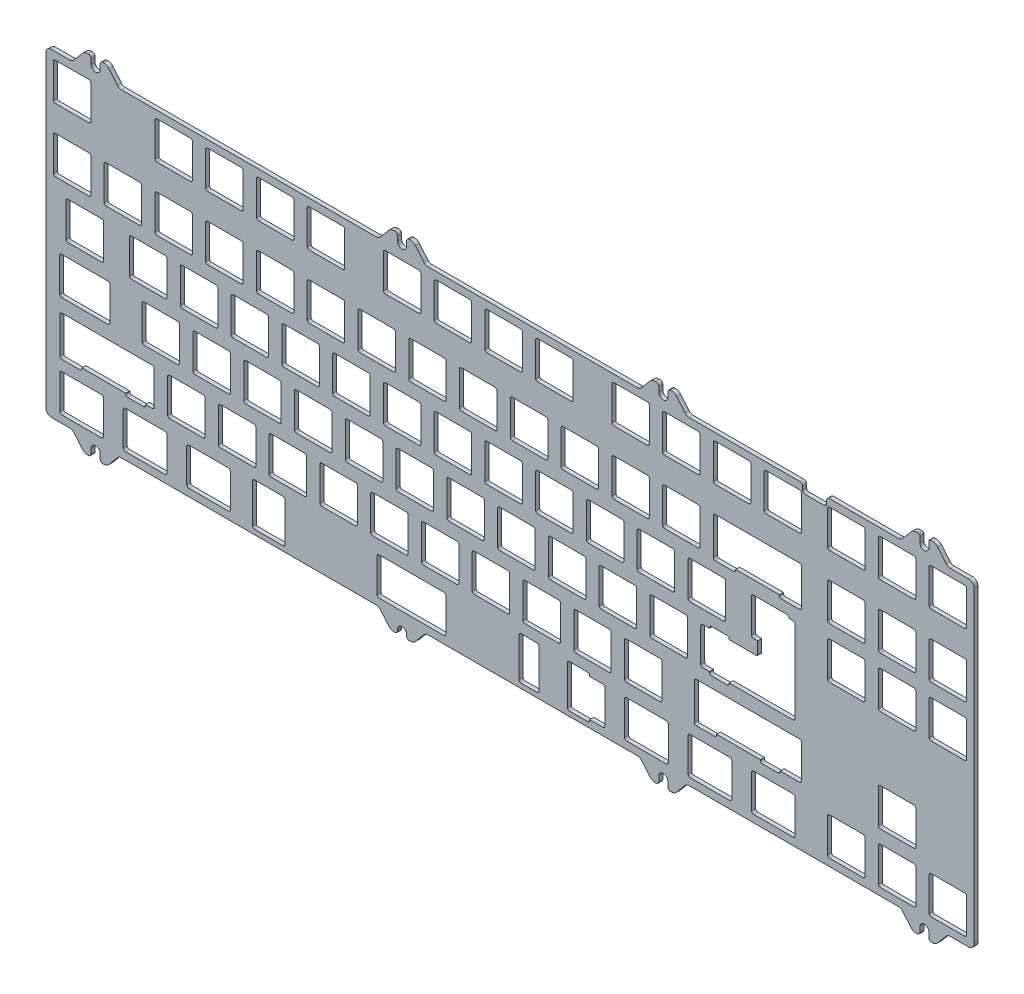
SolidWorks part; units mm, degrees
material "6061-T6 (SS)"
ref_plane "정면" through (0, 0, 0) normal (0, 0, 1) x (1, 0, 0)
ref_plane "윗면" through (0, 0, 0) normal (0, 1, 0) x (1, 0, 0)
ref_plane "우측면" through (0, 0, 0) normal (1, 0, 0) x (0, 0, -1)
sketch "스케치1" plane through (0, 0, 0) normal (0, 0, 1) x (1, 0, 0)
  line L450 (241.33, -16.7825) -> (273.02, -16.7825)
  line L451 (266.1131, -31.8325) -> (273.02, -31.8325)
  line L452 (231.5328, -109.8125) -> (310.0719, -109.8125)
  line L453 (234.2863, -73.9325) -> (272.92, -73.9325)
  line L454 (265.6692, -87.9825) -> (272.92, -87.9825)
  line L455 (255.7175, -92.9925) -> (270.5388, -92.9925)
  line L456 (255.7175, -107.0325) -> (270.5388, -107.0325)
  line L457 (260.37, -7.03) -> (273.03, -7.03)
  line L458 (260.37, 7.03) -> (273.03, 7.03)
  line L459 (231.5328, 9.8) -> (273.1063, 9.8)
  line L460 (246.5557, -68.9425) -> (270.5388, -68.9425)
  line L461 (255.6075, -35.8325) -> (268.2675, -35.8325)
  line L462 (18.5406, -109.8125) -> (114.1172, -109.8125)
  line L463 (27.0075, -68.9425) -> (39.6675, -68.9425)
  line L464 (27.0075, -54.8825) -> (39.6675, -54.8825)
  line L465 (31.77, -30.8425) -> (44.43, -30.8425)
  line L466 (31.77, -16.7825) -> (44.43, -16.7825)
  line L467 (31.77, -7.03) -> (44.43, -7.03)
  line L468 (31.77, 7.03) -> (44.43, 7.03)
  line L469 (18.5406, 9.8) -> (114.1172, 9.8)
  line L470 (-9.8, -107.8125) -> (-9.8, 7.8)
  line L471 (31.07, -17.4825) -> (31.07, -30.1425)
  line L472 (12.02, -17.4825) -> (12.02, -30.1425)
  line L473 (26.08, -17.4825) -> (26.08, -30.1425)
  line L474 (-7.03, -17.4825) -> (-7.03, -30.1425)
  line L475 (7.03, -17.4825) -> (7.03, -30.1425)
  line L476 (30.8125, -87.1825) -> (30.8125, -74.6325)
  line L477 (-4.6188, -88.2925) -> (-4.6188, -74.6325)
  line L478 (35.8325, -74.6325) -> (35.8325, -87.2925)
  line L479 (3.6682, -87.9925) -> (20.1443, -87.9925)
  line L480 (-3.8387, -92.9925) -> (10.9825, -92.9925)
  line L481 (-3.8387, -107.0325) -> (10.9825, -107.0325)
  line L482 (5.7546, -115.2125) -> (6.1328, -115.2125)
  line L483 (0.6572, -110.5269) -> (3.8395, -114.3195)
  line L484 (-0.8749, -109.8125) -> (-7.8, -109.8125)
  line L485 (2.9684, -88.9925) -> (-3.9188, -88.9925)
  line L486 (3.6682, -87.9925) -> (3.6684, -88.2921)
  line L487 (-4.6387, -93.7925) -> (-4.6387, -106.2325)
  line L488 (10.5328, -112.4125) -> (10.5328, -114.2125)
  line L489 (7.1328, -112.4125) -> (7.1328, -114.2125)
  line L490 (17.0085, -110.5269) -> (13.8262, -114.3195)
  line L491 (11.5328, -115.2125) -> (11.9111, -115.2125)
  line L492 (20.8441, -88.9925) -> (26.8442, -88.9925)
  line L493 (19.9738, -92.9925) -> (34.795, -92.9925)
  line L494 (19.9738, -107.0325) -> (34.795, -107.0325)
  line L495 (20.1443, -87.9925) -> (20.1441, -88.2921)
  line L496 (19.1738, -93.7925) -> (19.1738, -106.2325)
  line L497 (11.7825, -93.7925) -> (11.7825, -106.2325)
  line L498 (27.5442, -88.2925) -> (27.5442, -87.9825)
  line L499 (27.5442, -87.9825) -> (30.0125, -87.9825)
  line L500 (35.595, -93.7925) -> (35.595, -106.2325)
  line L501 (30.1125, -73.9325) -> (-3.9188, -73.9325)
  line L502 (-3.9488, -68.9425) -> (13.4737, -68.9425)
  line L503 (-3.9488, -54.8825) -> (13.4737, -54.8825)
  line L504 (-1.5675, -49.8925) -> (11.0925, -49.8925)
  line L505 (-1.5675, -35.8325) -> (11.0925, -35.8325)
  line L506 (-4.6488, -55.5825) -> (-4.6488, -68.2425)
  line L507 (-6.33, -30.8425) -> (6.33, -30.8425)
  line L508 (-2.2675, -36.5325) -> (-2.2675, -49.1925)
  line L509 (26.3075, -55.5825) -> (26.3075, -68.2425)
  line L510 (14.1737, -55.5825) -> (14.1737, -68.2425)
  line L511 (12.72, -30.8425) -> (25.38, -30.8425)
  line L512 (21.545, -36.5325) -> (21.545, -49.1925)
  line L513 (11.7925, -36.5325) -> (11.7925, -49.1925)
  line L514 (35.605, -36.5325) -> (35.605, -49.1925)
  line L515 (22.245, -49.8925) -> (34.905, -49.8925)
  line L516 (22.245, -35.8325) -> (34.905, -35.8325)
  line L517 (-7.03, 6.33) -> (-7.03, -6.33)
  line L518 (7.03, 6.33) -> (7.03, -6.33)
  line L519 (-6.33, -16.7825) -> (6.33, -16.7825)
  line L520 (-6.33, -7.03) -> (6.33, -7.03)
  line L521 (-0.8749, 9.8) -> (-7.8, 9.8)
  line L522 (-6.33, 7.03) -> (6.33, 7.03)
  line L523 (5.7546, 15.2) -> (6.1328, 15.2)
  line L524 (0.6572, 10.5144) -> (3.8395, 14.307)
  line L525 (31.07, 6.33) -> (31.07, -6.33)
  line L526 (12.72, -16.7825) -> (25.38, -16.7825)
  line L527 (11.5328, 15.2) -> (11.9111, 15.2)
  line L528 (10.5328, 12.4) -> (10.5328, 14.2)
  line L529 (7.1328, 12.4) -> (7.1328, 14.2)
  line L530 (17.0085, 10.5144) -> (13.8262, 14.307)
  line L531 (240.63, -17.4825) -> (240.63, -31.1325)
  line L532 (221.57, -17.4825) -> (221.57, -30.1425)
  line L533 (235.63, -17.4825) -> (235.63, -30.1425)
  line L534 (202.52, -17.4825) -> (202.52, -30.1425)
  line L535 (216.58, -17.4825) -> (216.58, -30.1425)
  line L536 (183.47, -17.4825) -> (183.47, -30.1425)
  line L537 (197.53, -17.4825) -> (197.53, -30.1425)
  line L538 (164.42, -17.4825) -> (164.42, -30.1425)
  line L539 (178.48, -17.4825) -> (178.48, -30.1425)
  line L540 (145.37, -17.4825) -> (145.37, -30.1425)
  line L541 (159.43, -17.4825) -> (159.43, -30.1425)
  line L542 (126.32, -17.4825) -> (126.32, -30.1425)
  line L543 (140.38, -17.4825) -> (140.38, -30.1425)
  line L544 (107.27, -17.4825) -> (107.27, -30.1425)
  line L545 (121.33, -17.4825) -> (121.33, -30.1425)
  line L546 (88.22, -17.4825) -> (88.22, -30.1425)
  line L547 (102.28, -17.4825) -> (102.28, -30.1425)
  line L548 (69.17, -17.4825) -> (69.17, -30.1425)
  line L549 (83.23, -17.4825) -> (83.23, -30.1425)
  line L550 (50.12, -17.4825) -> (50.12, -30.1425)
  line L551 (64.18, -17.4825) -> (64.18, -30.1425)
  line L552 (45.13, -17.4825) -> (45.13, -30.1425)
  line L553 (133.5328, -109.8125) -> (212.1172, -109.8125)
  line L554 (150.8325, -87.9925) -> (163.4925, -87.9925)
  line L555 (150.8325, -73.9325) -> (163.4925, -73.9325)
  line L556 (141.3075, -68.9425) -> (153.9675, -68.9425)
  line L557 (141.3075, -54.8825) -> (153.9675, -54.8825)
  line L558 (146.07, -30.8425) -> (158.73, -30.8425)
  line L559 (93.6825, -87.9925) -> (106.3425, -87.9925)
  line L560 (93.6825, -73.9325) -> (106.3425, -73.9325)
  line L561 (84.1575, -68.9425) -> (96.8175, -68.9425)
  line L562 (84.1575, -54.8825) -> (96.8175, -54.8825)
  line L563 (88.92, -30.8425) -> (101.58, -30.8425)
  line L564 (92.9825, -74.6325) -> (92.9825, -87.2925)
  line L565 (73.9325, -74.6325) -> (73.9325, -87.2925)
  line L566 (87.9925, -74.6325) -> (87.9925, -87.2925)
  line L567 (54.8825, -74.6325) -> (54.8825, -87.2925)
  line L568 (68.9425, -74.6325) -> (68.9425, -87.2925)
  line L569 (49.8925, -74.6325) -> (49.8925, -87.2925)
  line L570 (55.5825, -87.9925) -> (68.2425, -87.9925)
  line L571 (43.7863, -92.9925) -> (58.6075, -92.9925)
  line L572 (43.7863, -107.0325) -> (58.6075, -107.0325)
  line L573 (42.9863, -93.7925) -> (42.9863, -106.2325)
  line L574 (36.5325, -87.9925) -> (49.1925, -87.9925)
  line L575 (59.4075, -93.7925) -> (59.4075, -106.2325)
  line L576 (74.6325, -87.9925) -> (87.2925, -87.9925)
  line L577 (68.374, -91.9925) -> (79.1683, -91.9925)
  line L578 (68.374, -108.0325) -> (79.1683, -108.0325)
  line L579 (67.674, -107.3325) -> (67.674, -92.6925)
  line L580 (79.8683, -107.3325) -> (79.8683, -92.6925)
  line L581 (55.5825, -73.9325) -> (68.2425, -73.9325)
  line L582 (60.345, -49.8925) -> (73.005, -49.8925)
  line L583 (60.345, -35.8325) -> (73.005, -35.8325)
  line L584 (64.4075, -55.5825) -> (64.4075, -68.2425)
  line L585 (45.3575, -55.5825) -> (45.3575, -68.2425)
  line L586 (59.4175, -55.5825) -> (59.4175, -68.2425)
  line L587 (40.3675, -55.5825) -> (40.3675, -68.2425)
  line L588 (46.0575, -68.9425) -> (58.7175, -68.9425)
  line L589 (36.5325, -73.9325) -> (49.1925, -73.9325)
  line L590 (46.0575, -54.8825) -> (58.7175, -54.8825)
  line L591 (41.295, -49.8925) -> (53.955, -49.8925)
  line L592 (41.295, -35.8325) -> (53.955, -35.8325)
  line L593 (40.595, -36.5325) -> (40.595, -49.1925)
  line L594 (59.645, -36.5325) -> (59.645, -49.1925)
  line L595 (54.655, -36.5325) -> (54.655, -49.1925)
  line L596 (50.82, -30.8425) -> (63.48, -30.8425)
  line L597 (83.4575, -55.5825) -> (83.4575, -68.2425)
  line L598 (78.4675, -55.5825) -> (78.4675, -68.2425)
  line L599 (74.6325, -73.9325) -> (87.2925, -73.9325)
  line L600 (65.1075, -68.9425) -> (77.7675, -68.9425)
  line L601 (69.87, -30.8425) -> (82.53, -30.8425)
  line L602 (65.1075, -54.8825) -> (77.7675, -54.8825)
  line L603 (78.695, -36.5325) -> (78.695, -49.1925)
  line L604 (73.705, -36.5325) -> (73.705, -49.1925)
  line L605 (92.755, -36.5325) -> (92.755, -49.1925)
  line L606 (79.395, -49.8925) -> (92.055, -49.8925)
  line L607 (79.395, -35.8325) -> (92.055, -35.8325)
  line L608 (150.1325, -74.6325) -> (150.1325, -87.2925)
  line L609 (131.0825, -74.6325) -> (131.0825, -87.2925)
  line L610 (145.1425, -74.6325) -> (145.1425, -87.2925)
  line L611 (112.0325, -74.6325) -> (112.0325, -87.2925)
  line L612 (126.0925, -74.6325) -> (126.0925, -87.2925)
  line L613 (107.0425, -74.6325) -> (107.0425, -87.2925)
  line L614 (115.2238, -92.9925) -> (139.57, -92.9925)
  line L615 (115.2238, -107.0325) -> (139.57, -107.0325)
  line L616 (112.7325, -87.9925) -> (125.3925, -87.9925)
  line L617 (122.125, -113.7125) -> (122.125, -114.2125)
  line L618 (115.6493, -110.5269) -> (118.8316, -114.3195)
  line L619 (120.7468, -115.2125) -> (121.125, -115.2125)
  line L620 (114.4238, -93.7925) -> (114.4238, -106.2325)
  line L621 (125.525, -113.7125) -> (125.525, -114.2125)
  line L622 (132.0007, -110.5269) -> (128.8184, -114.3195)
  line L623 (126.525, -115.2125) -> (126.9033, -115.2125)
  line L624 (131.7825, -87.9925) -> (144.4425, -87.9925)
  line L625 (140.37, -93.7925) -> (140.37, -106.2325)
  line L626 (112.7325, -73.9325) -> (125.3925, -73.9325)
  line L627 (122.2575, -68.9425) -> (134.9175, -68.9425)
  line L628 (122.2575, -54.8825) -> (134.9175, -54.8825)
  line L629 (117.495, -49.8925) -> (130.155, -49.8925)
  line L630 (117.495, -35.8325) -> (130.155, -35.8325)
  line L631 (121.5575, -55.5825) -> (121.5575, -68.2425)
  line L632 (102.5075, -55.5825) -> (102.5075, -68.2425)
  line L633 (116.5675, -55.5825) -> (116.5675, -68.2425)
  line L634 (97.5175, -55.5825) -> (97.5175, -68.2425)
  line L635 (103.2075, -68.9425) -> (115.8675, -68.9425)
  line L636 (103.2075, -54.8825) -> (115.8675, -54.8825)
  line L637 (98.445, -49.8925) -> (111.105, -49.8925)
  line L638 (98.445, -35.8325) -> (111.105, -35.8325)
  line L639 (107.97, -30.8425) -> (120.63, -30.8425)
  line L640 (97.745, -36.5325) -> (97.745, -49.1925)
  line L641 (116.795, -36.5325) -> (116.795, -49.1925)
  line L642 (111.805, -36.5325) -> (111.805, -49.1925)
  line L643 (140.6075, -55.5825) -> (140.6075, -68.2425)
  line L644 (135.6175, -55.5825) -> (135.6175, -68.2425)
  line L645 (131.7825, -73.9325) -> (144.4425, -73.9325)
  line L646 (136.545, -49.8925) -> (149.205, -49.8925)
  line L647 (136.545, -35.8325) -> (149.205, -35.8325)
  line L648 (127.02, -30.8425) -> (139.68, -30.8425)
  line L649 (135.845, -36.5325) -> (135.845, -49.1925)
  line L650 (130.855, -36.5325) -> (130.855, -49.1925)
  line L651 (149.905, -36.5325) -> (149.905, -49.1925)
  line L652 (208.0925, -92.9925) -> (222.9138, -92.9925)
  line L653 (208.0925, -107.0325) -> (222.9138, -107.0325)
  line L654 (207.9825, -87.9925) -> (220.6425, -87.9925)
  line L655 (207.9825, -73.9325) -> (220.6425, -73.9325)
  line L656 (198.4575, -54.8825) -> (211.1175, -54.8825)
  line L657 (203.22, -30.8425) -> (215.88, -30.8425)
  line L658 (198.4575, -68.9425) -> (211.1175, -68.9425)
  line L659 (207.2825, -74.6325) -> (207.2825, -87.2925)
  line L660 (188.2325, -74.6325) -> (188.2325, -87.2925)
  line L661 (202.2925, -74.6325) -> (202.2925, -87.2925)
  line L662 (169.1825, -74.6325) -> (169.1825, -87.2925)
  line L663 (183.2425, -74.6325) -> (183.2425, -87.2925)
  line L664 (164.1925, -74.6325) -> (164.1925, -87.2925)
  line L665 (169.8825, -87.9925) -> (182.5425, -87.9925)
  line L666 (174.45, -108.0325) -> (168.45, -108.0325)
  line L667 (168.45, -91.9925) -> (174.45, -91.9925)
  line L668 (175.15, -107.3325) -> (175.15, -92.6925)
  line L669 (167.75, -107.3325) -> (167.75, -92.6925)
  line L670 (199.1013, -92.9925) -> (194.168, -92.9925)
  line L671 (188.9325, -87.9925) -> (201.5925, -87.9925)
  line L672 (194.168, -107.0325) -> (199.1013, -107.0325)
  line L673 (186.5613, -91.9925) -> (193.468, -91.9925)
  line L674 (194.168, -107.0325) -> (194.168, -107.3325)
  line L675 (186.5613, -108.0325) -> (193.468, -108.0325)
  line L676 (194.168, -92.9925) -> (194.168, -92.6925)
  line L677 (185.8613, -92.6925) -> (185.8613, -107.3325)
  line L678 (199.9013, -93.7925) -> (199.9013, -106.2325)
  line L679 (207.2925, -93.7925) -> (207.2925, -106.2325)
  line L680 (169.8825, -73.9325) -> (182.5425, -73.9325)
  line L681 (179.4075, -68.9425) -> (192.0675, -68.9425)
  line L682 (179.4075, -54.8825) -> (192.0675, -54.8825)
  line L683 (174.645, -49.8925) -> (187.305, -49.8925)
  line L684 (174.645, -35.8325) -> (187.305, -35.8325)
  line L685 (178.7075, -55.5825) -> (178.7075, -68.2425)
  line L686 (159.6575, -55.5825) -> (159.6575, -68.2425)
  line L687 (173.7175, -55.5825) -> (173.7175, -68.2425)
  line L688 (154.6675, -55.5825) -> (154.6675, -68.2425)
  line L689 (160.3575, -68.9425) -> (173.0175, -68.9425)
  line L690 (160.3575, -54.8825) -> (173.0175, -54.8825)
  line L691 (155.595, -49.8925) -> (168.255, -49.8925)
  line L692 (155.595, -35.8325) -> (168.255, -35.8325)
  line L693 (165.12, -30.8425) -> (177.78, -30.8425)
  line L694 (154.895, -36.5325) -> (154.895, -49.1925)
  line L695 (173.945, -36.5325) -> (173.945, -49.1925)
  line L696 (168.955, -36.5325) -> (168.955, -49.1925)
  line L697 (192.7675, -55.5825) -> (192.7675, -68.2425)
  line L698 (197.7575, -55.5825) -> (197.7575, -68.2425)
  line L699 (188.9325, -73.9325) -> (201.5925, -73.9325)
  line L700 (193.695, -49.8925) -> (206.355, -49.8925)
  line L701 (193.695, -35.8325) -> (206.355, -35.8325)
  line L702 (184.17, -30.8425) -> (196.83, -30.8425)
  line L703 (192.995, -36.5325) -> (192.995, -49.1925)
  line L704 (188.005, -36.5325) -> (188.005, -49.1925)
  line L705 (207.055, -36.5325) -> (207.055, -49.1925)
  line L706 (233.4863, -74.7325) -> (233.4863, -88.2925)
  line L707 (221.3425, -74.6325) -> (221.3425, -87.2925)
  line L708 (234.1863, -88.9925) -> (241.0932, -88.9925)
  line L709 (231.905, -92.9925) -> (246.7263, -92.9925)
  line L710 (231.905, -107.0325) -> (246.7263, -107.0325)
  line L711 (223.525, -112.4125) -> (223.525, -114.2125)
  line L712 (220.125, -112.4125) -> (220.125, -114.2125)
  line L713 (213.6493, -110.5269) -> (216.8316, -114.3195)
  line L714 (219.125, -115.2125) -> (218.7468, -115.2125)
  line L715 (230.0007, -110.5269) -> (226.8184, -114.3195)
  line L716 (224.9033, -115.2125) -> (224.525, -115.2125)
  line L717 (231.105, -93.7925) -> (231.105, -106.2325)
  line L718 (223.7138, -93.7925) -> (223.7138, -106.2325)
  line L719 (241.7932, -87.9925) -> (258.2693, -87.9925)
  line L720 (241.7932, -88.2925) -> (241.7932, -87.9925)
  line L721 (247.5263, -93.7925) -> (247.5263, -106.2325)
  line L722 (258.9693, -88.9925) -> (264.9692, -88.9925)
  line L723 (258.2693, -88.2925) -> (258.2693, -87.9925)
  line L724 (265.6692, -88.2925) -> (265.6692, -87.9825)
  line L725 (254.9175, -93.7925) -> (254.9175, -106.2325)
  line L726 (231.795, -49.8925) -> (244.455, -49.8925)
  line L727 (231.795, -35.8325) -> (244.455, -35.8325)
  line L728 (236.6675, -68.9425) -> (239.1558, -68.9425)
  line L729 (236.6675, -54.8825) -> (239.1558, -54.8825)
  line L730 (216.8075, -55.5825) -> (216.8075, -68.2425)
  line L731 (230.8675, -55.5825) -> (230.8675, -68.2425)
  line L732 (211.8175, -55.5825) -> (211.8175, -68.2425)
  line L733 (217.5075, -68.9425) -> (230.1675, -68.9425)
  line L734 (235.8675, -55.6825) -> (235.8675, -68.1425)
  line L735 (212.745, -49.8925) -> (225.405, -49.8925)
  line L736 (212.745, -35.8325) -> (225.405, -35.8325)
  line L737 (222.27, -30.8425) -> (234.93, -30.8425)
  line L738 (217.5075, -54.8825) -> (230.1675, -54.8825)
  line L739 (212.045, -36.5325) -> (212.045, -49.1925)
  line L740 (231.095, -36.5325) -> (231.095, -49.1925)
  line L741 (226.105, -36.5325) -> (226.105, -49.1925)
  line L742 (239.8558, -69.9425) -> (245.8557, -69.9425)
  line L743 (246.5557, -69.2425) -> (246.5557, -68.9425)
  line L744 (239.1558, -69.2425) -> (239.1558, -68.9425)
  line L745 (248.937, -30.8325) -> (265.4131, -30.8325)
  line L746 (246.5557, -54.8825) -> (256.767, -54.8825)
  line L747 (248.937, -31.1325) -> (248.937, -30.8325)
  line L748 (241.33, -31.8325) -> (248.237, -31.8325)
  line L749 (239.8558, -53.8825) -> (245.8557, -53.8825)
  line L750 (246.5557, -54.5825) -> (246.5557, -54.8825)
  line L751 (239.1558, -54.5825) -> (239.1558, -54.8825)
  line L752 (245.155, -36.5325) -> (245.155, -49.1925)
  line L753 (265.4131, -31.1325) -> (265.4131, -30.8325)
  line L754 (254.9075, -36.5325) -> (254.9075, -49.1925)
  line L755 (255.6075, -49.8925) -> (257.267, -49.8925)
  line L756 (257.267, -49.8925) -> (257.267, -54.3825)
  line L757 (146.07, -16.7825) -> (158.73, -16.7825)
  line L758 (133.5328, 9.8) -> (212.1172, 9.8)
  line L759 (88.92, -16.7825) -> (101.58, -16.7825)
  line L760 (88.92, -7.03) -> (101.58, -7.03)
  line L761 (88.92, 7.03) -> (101.58, 7.03)
  line L762 (50.12, 6.33) -> (50.12, -6.33)
  line L763 (64.18, 6.33) -> (64.18, -6.33)
  line L764 (45.13, 6.33) -> (45.13, -6.33)
  line L765 (50.82, -16.7825) -> (63.48, -16.7825)
  line L766 (50.82, -7.03) -> (63.48, -7.03)
  line L767 (50.82, 7.03) -> (63.48, 7.03)
  line L768 (88.22, 6.33) -> (88.22, -6.33)
  line L769 (69.17, 6.33) -> (69.17, -6.33)
  line L770 (83.23, 6.33) -> (83.23, -6.33)
  line L771 (69.87, -16.7825) -> (82.53, -16.7825)
  line L772 (69.87, -7.03) -> (82.53, -7.03)
  line L773 (69.87, 7.03) -> (82.53, 7.03)
  line L774 (117.495, -7.03) -> (130.155, -7.03)
  line L775 (117.495, 7.03) -> (130.155, 7.03)
  line L776 (116.795, 6.33) -> (116.795, -6.33)
  line L777 (102.28, 6.33) -> (102.28, -6.33)
  line L778 (107.97, -16.7825) -> (120.63, -16.7825)
  line L779 (122.125, 12.4) -> (122.125, 14.2)
  line L780 (120.7468, 15.2) -> (121.125, 15.2)
  line L781 (115.6493, 10.5144) -> (118.8316, 14.307)
  line L782 (135.845, 6.33) -> (135.845, -6.33)
  line L783 (149.905, 6.33) -> (149.905, -6.33)
  line L784 (130.855, 6.33) -> (130.855, -6.33)
  line L785 (127.02, -16.7825) -> (139.68, -16.7825)
  line L786 (136.545, -7.03) -> (149.205, -7.03)
  line L787 (136.545, 7.03) -> (149.205, 7.03)
  line L788 (125.525, 12.4) -> (125.525, 14.2)
  line L789 (126.525, 15.2) -> (126.9033, 15.2)
  line L790 (132.0007, 10.5144) -> (128.8184, 14.307)
  line L791 (203.22, -16.7825) -> (215.88, -16.7825)
  line L792 (203.22, -7.03) -> (215.88, -7.03)
  line L793 (203.22, 7.03) -> (215.88, 7.03)
  line L794 (174.645, -7.03) -> (187.305, -7.03)
  line L795 (174.645, 7.03) -> (187.305, 7.03)
  line L796 (173.945, 6.33) -> (173.945, -6.33)
  line L797 (154.895, 6.33) -> (154.895, -6.33)
  line L798 (168.955, 6.33) -> (168.955, -6.33)
  line L799 (165.12, -16.7825) -> (177.78, -16.7825)
  line L800 (155.595, -7.03) -> (168.255, -7.03)
  line L801 (155.595, 7.03) -> (168.255, 7.03)
  line L802 (202.52, 6.33) -> (202.52, -6.33)
  line L803 (188.005, 6.33) -> (188.005, -6.33)
  line L804 (184.17, -16.7825) -> (196.83, -16.7825)
  line L805 (221.57, 6.33) -> (221.57, -6.33)
  line L806 (235.63, 6.33) -> (235.63, -6.33)
  line L807 (216.58, 6.33) -> (216.58, -6.33)
  line L808 (222.27, -16.7825) -> (234.93, -16.7825)
  line L809 (222.27, -7.03) -> (234.93, -7.03)
  line L810 (222.27, 7.03) -> (234.93, 7.03)
  line L811 (223.525, 12.4) -> (223.525, 14.2)
  line L812 (219.125, 15.2) -> (218.7468, 15.2)
  line L813 (220.125, 12.4) -> (220.125, 14.2)
  line L814 (213.6493, 10.5144) -> (216.8316, 14.307)
  line L815 (224.9033, 15.2) -> (224.525, 15.2)
  line L816 (230.0007, 10.5144) -> (226.8184, 14.307)
  line L817 (259.67, 6.33) -> (259.67, -6.33)
  line L818 (240.62, 6.33) -> (240.62, -6.33)
  line L819 (254.68, 6.33) -> (254.68, -6.33)
  line L820 (241.32, -7.03) -> (253.98, -7.03)
  line L821 (241.32, 7.03) -> (253.98, 7.03)
  line L822 (273.72, -17.4825) -> (273.72, -31.1325)
  line L823 (338.4125, -107.8125) -> (338.4125, 7.8)
  line L824 (321.5825, -17.4825) -> (321.5825, -30.1425)
  line L825 (335.6425, -17.4825) -> (335.6425, -30.1425)
  line L826 (302.5325, -17.4825) -> (302.5325, -30.1425)
  line L827 (316.5925, -17.4825) -> (316.5925, -30.1425)
  line L828 (283.4825, -17.4825) -> (283.4825, -30.1425)
  line L829 (297.5425, -17.4825) -> (297.5425, -30.1425)
  line L830 (322.2825, -107.0425) -> (334.9425, -107.0425)
  line L831 (322.2825, -92.9825) -> (334.9425, -92.9825)
  line L832 (322.2825, -49.8925) -> (334.9425, -49.8925)
  line L833 (322.2825, -35.8325) -> (334.9425, -35.8325)
  line L834 (322.2825, -30.8425) -> (334.9425, -30.8425)
  line L835 (302.5325, -74.6325) -> (302.5325, -87.2925)
  line L836 (316.5925, -74.6325) -> (316.5925, -87.2925)
  line L837 (273.72, -74.7325) -> (273.72, -87.1825)
  line L838 (284.1825, -107.0425) -> (296.8425, -107.0425)
  line L839 (284.1825, -92.9825) -> (296.8425, -92.9825)
  line L840 (271.3388, -93.7925) -> (271.3388, -106.2325)
  line L841 (283.4825, -93.6825) -> (283.4825, -106.3425)
  line L842 (322.8579, -115.2125) -> (322.4797, -115.2125)
  line L843 (321.4797, -112.4125) -> (321.4797, -114.2125)
  line L844 (318.0797, -112.4125) -> (318.0797, -114.2125)
  line L845 (311.604, -110.5269) -> (314.7863, -114.3195)
  line L846 (317.0797, -115.2125) -> (316.7014, -115.2125)
  line L847 (303.2325, -107.0425) -> (315.8925, -107.0425)
  line L848 (303.2325, -92.9825) -> (315.8925, -92.9825)
  line L849 (303.2325, -87.9925) -> (315.8925, -87.9925)
  line L850 (302.5325, -93.6825) -> (302.5325, -106.3425)
  line L851 (297.5425, -93.6825) -> (297.5425, -106.3425)
  line L852 (321.5825, -93.6825) -> (321.5825, -106.3425)
  line L853 (316.5925, -93.6825) -> (316.5925, -106.3425)
  line L854 (284.1825, -49.8925) -> (296.8425, -49.8925)
  line L855 (284.1825, -35.8325) -> (296.8425, -35.8325)
  line L856 (284.1825, -30.8425) -> (296.8425, -30.8425)
  line L857 (271.3388, -37.5495) -> (271.3388, -68.1425)
  line L858 (268.9675, -36.5325) -> (268.9675, -36.7495)
  line L859 (268.9675, -36.7495) -> (270.5388, -36.7495)
  line L860 (283.4825, -36.5325) -> (283.4825, -49.1925)
  line L861 (303.2325, -73.9325) -> (315.8925, -73.9325)
  line L862 (303.2325, -49.8925) -> (315.8925, -49.8925)
  line L863 (303.2325, -35.8325) -> (315.8925, -35.8325)
  line L864 (303.2325, -30.8425) -> (315.8925, -30.8425)
  line L865 (302.5325, -36.5325) -> (302.5325, -49.1925)
  line L866 (297.5425, -36.5325) -> (297.5425, -49.1925)
  line L867 (321.5825, -36.5325) -> (321.5825, -49.1925)
  line L868 (316.5925, -36.5325) -> (316.5925, -49.1925)
  line L869 (327.9553, -110.5269) -> (324.773, -114.3195)
  line L870 (335.6425, -93.6825) -> (335.6425, -106.3425)
  line L871 (329.4874, -109.8125) -> (336.4125, -109.8125)
  line L872 (335.6425, -36.5325) -> (335.6425, -49.1925)
  line L873 (322.2825, -16.7825) -> (334.9425, -16.7825)
  line L874 (322.2825, -7.03) -> (334.9425, -7.03)
  line L875 (322.2825, 7.03) -> (334.9425, 7.03)
  line L876 (284.1825, -16.7825) -> (296.8425, -16.7825)
  line L877 (284.1825, -7.03) -> (296.8425, -7.03)
  line L878 (284.1825, 7.03) -> (296.8425, 7.03)
  line L879 (284.1063, 9.8) -> (310.0719, 9.8)
  line L880 (283.4825, 6.33) -> (283.4825, -6.33)
  line L881 (273.73, 6.33) -> (273.73, -6.33)
  line L882 (275.1063, 6.6) -> (282.1063, 6.6)
  line L883 (274.1063, 7.6) -> (274.1063, 8.8)
  line L884 (283.1063, 8.8) -> (283.1063, 7.6)
  line L885 (321.5825, 6.33) -> (321.5825, -6.33)
  line L886 (302.5325, 6.33) -> (302.5325, -6.33)
  line L887 (316.5925, 6.33) -> (316.5925, -6.33)
  line L888 (297.5425, 6.33) -> (297.5425, -6.33)
  line L889 (303.2325, -16.7825) -> (315.8925, -16.7825)
  line L890 (303.2325, -7.03) -> (315.8925, -7.03)
  line L891 (303.2325, 7.03) -> (315.8925, 7.03)
  line L892 (321.4797, 12.4) -> (321.4797, 14.7)
  line L893 (322.8579, 15.2) -> (321.9797, 15.2)
  line L894 (318.0797, 12.4) -> (318.0797, 14.7)
  line L895 (317.5797, 15.2) -> (316.7014, 15.2)
  line L896 (311.604, 10.5144) -> (314.7863, 14.307)
  line L897 (335.6425, 6.33) -> (335.6425, -6.33)
  line L898 (327.9553, 10.5144) -> (324.773, 14.307)
  line L899 (329.4874, 9.8) -> (336.4125, 9.8)
  arc A434 (36.5325, -73.9325) -> (35.8325, -74.6325) centre (36.5325, -74.6325) ccw
  arc A435 (35.8325, -87.2925) -> (36.5325, -87.9925) centre (36.5325, -87.2925) ccw
  arc A436 (6.1328, -115.2125) -> (7.1328, -114.2125) centre (6.1328, -114.2125) ccw
  arc A437 (0.6572, -110.5269) -> (-0.8749, -109.8125) centre (-0.8749, -111.8125) ccw
  arc A438 (3.8395, -114.3195) -> (5.7546, -115.2125) centre (5.7546, -112.7125) ccw
  arc A439 (-9.8, -107.8125) -> (-7.8, -109.8125) centre (-7.8, -107.8125) ccw
  arc A440 (-4.6188, -88.2925) -> (-3.9188, -88.9925) centre (-3.9188, -88.2925) ccw
  arc A441 (2.9684, -88.9925) -> (3.6684, -88.2921) centre (2.9684, -88.2925) ccw
  arc A442 (-3.8387, -92.9925) -> (-4.6387, -93.7925) centre (-3.8387, -93.7925) ccw
  arc A443 (-4.6387, -106.2325) -> (-3.8387, -107.0325) centre (-3.8387, -106.2325) ccw
  arc A444 (18.5406, -109.8125) -> (17.0085, -110.5269) centre (18.5406, -111.8125) ccw
  arc A445 (10.5328, -112.4125) -> (7.1328, -112.4125) centre (8.8328, -112.4125) ccw
  arc A446 (11.9111, -115.2125) -> (13.8262, -114.3195) centre (11.9111, -112.7125) ccw
  arc A447 (10.5328, -114.2125) -> (11.5328, -115.2125) centre (11.5328, -114.2125) ccw
  arc A448 (20.1441, -88.2921) -> (20.8441, -88.9925) centre (20.8441, -88.2925) ccw
  arc A449 (19.1738, -106.2325) -> (19.9738, -107.0325) centre (19.9738, -106.2325) ccw
  arc A450 (19.9738, -92.9925) -> (19.1738, -93.7925) centre (19.9738, -93.7925) ccw
  arc A451 (11.7825, -93.7925) -> (10.9825, -92.9925) centre (10.9825, -93.7925) ccw
  arc A452 (10.9825, -107.0325) -> (11.7825, -106.2325) centre (10.9825, -106.2325) ccw
  arc A453 (26.8442, -88.9925) -> (27.5442, -88.2925) centre (26.8442, -88.2925) ccw
  arc A454 (30.0125, -87.9825) -> (30.8125, -87.1825) centre (30.0125, -87.1825) ccw
  arc A455 (34.795, -107.0325) -> (35.595, -106.2325) centre (34.795, -106.2325) ccw
  arc A456 (35.595, -93.7925) -> (34.795, -92.9925) centre (34.795, -93.7925) ccw
  arc A457 (6.33, -30.8425) -> (7.03, -30.1425) centre (6.33, -30.1425) ccw
  arc A458 (-3.9188, -73.9325) -> (-4.6188, -74.6325) centre (-3.9188, -74.6325) ccw
  arc A459 (-4.6488, -68.2425) -> (-3.9488, -68.9425) centre (-3.9488, -68.2425) ccw
  arc A460 (-7.03, -30.1425) -> (-6.33, -30.8425) centre (-6.33, -30.1425) ccw
  arc A461 (-3.9488, -54.8825) -> (-4.6488, -55.5825) centre (-3.9488, -55.5825) ccw
  arc A462 (-1.5675, -35.8325) -> (-2.2675, -36.5325) centre (-1.5675, -36.5325) ccw
  arc A463 (-2.2675, -49.1925) -> (-1.5675, -49.8925) centre (-1.5675, -49.1925) ccw
  arc A464 (13.4737, -68.9425) -> (14.1737, -68.2425) centre (13.4737, -68.2425) ccw
  arc A465 (30.8125, -74.6325) -> (30.1125, -73.9325) centre (30.1125, -74.6325) ccw
  arc A466 (26.3075, -68.2425) -> (27.0075, -68.9425) centre (27.0075, -68.2425) ccw
  arc A467 (22.245, -35.8325) -> (21.545, -36.5325) centre (22.245, -36.5325) ccw
  arc A468 (21.545, -49.1925) -> (22.245, -49.8925) centre (22.245, -49.1925) ccw
  arc A469 (12.02, -30.1425) -> (12.72, -30.8425) centre (12.72, -30.1425) ccw
  arc A470 (14.1737, -55.5825) -> (13.4737, -54.8825) centre (13.4737, -55.5825) ccw
  arc A471 (11.7925, -36.5325) -> (11.0925, -35.8325) centre (11.0925, -36.5325) ccw
  arc A472 (11.0925, -49.8925) -> (11.7925, -49.1925) centre (11.0925, -49.1925) ccw
  arc A473 (27.0075, -54.8825) -> (26.3075, -55.5825) centre (27.0075, -55.5825) ccw
  arc A474 (35.605, -36.5325) -> (34.905, -35.8325) centre (34.905, -36.5325) ccw
  arc A475 (34.905, -49.8925) -> (35.605, -49.1925) centre (34.905, -49.1925) ccw
  arc A476 (31.07, -30.1425) -> (31.77, -30.8425) centre (31.77, -30.1425) ccw
  arc A477 (25.38, -30.8425) -> (26.08, -30.1425) centre (25.38, -30.1425) ccw
  arc A478 (7.03, -17.4825) -> (6.33, -16.7825) centre (6.33, -17.4825) ccw
  arc A479 (7.03, 6.33) -> (6.33, 7.03) centre (6.33, 6.33) ccw
  arc A480 (6.33, -7.03) -> (7.03, -6.33) centre (6.33, -6.33) ccw
  arc A481 (7.1328, 14.2) -> (6.1328, 15.2) centre (6.1328, 14.2) ccw
  arc A482 (-6.33, -16.7825) -> (-7.03, -17.4825) centre (-6.33, -17.4825) ccw
  arc A483 (-7.03, -6.33) -> (-6.33, -7.03) centre (-6.33, -6.33) ccw
  arc A484 (-7.8, 9.8) -> (-9.8, 7.8) centre (-7.8, 7.8) ccw
  arc A485 (-6.33, 7.03) -> (-7.03, 6.33) centre (-6.33, 6.33) ccw
  arc A486 (5.7546, 15.2) -> (3.8395, 14.307) centre (5.7546, 12.7) ccw
  arc A487 (-0.8749, 9.8) -> (0.6572, 10.5144) centre (-0.8749, 11.8) ccw
  arc A488 (12.72, -16.7825) -> (12.02, -17.4825) centre (12.72, -17.4825) ccw
  arc A489 (31.77, -16.7825) -> (31.07, -17.4825) centre (31.77, -17.4825) ccw
  arc A490 (26.08, -17.4825) -> (25.38, -16.7825) centre (25.38, -17.4825) ccw
  arc A491 (31.07, -6.33) -> (31.77, -7.03) centre (31.77, -6.33) ccw
  arc A492 (17.0085, 10.5144) -> (18.5406, 9.8) centre (18.5406, 11.8) ccw
  arc A493 (13.8262, 14.307) -> (11.9111, 15.2) centre (11.9111, 12.7) ccw
  arc A494 (11.5328, 15.2) -> (10.5328, 14.2) centre (11.5328, 14.2) ccw
  arc A495 (7.1328, 12.4) -> (10.5328, 12.4) centre (8.8328, 12.3995) ccw
  arc A496 (31.77, 7.03) -> (31.07, 6.33) centre (31.77, 6.33) ccw
  arc A497 (43.7863, -92.9925) -> (42.9863, -93.7925) centre (43.7863, -93.7925) ccw
  arc A498 (42.9863, -106.2325) -> (43.7863, -107.0325) centre (43.7863, -106.2325) ccw
  arc A499 (49.1925, -87.9925) -> (49.8925, -87.2925) centre (49.1925, -87.2925) ccw
  arc A500 (59.4075, -93.7925) -> (58.6075, -92.9925) centre (58.6075, -93.7925) ccw
  arc A501 (58.6075, -107.0325) -> (59.4075, -106.2325) centre (58.6075, -106.2325) ccw
  arc A502 (54.8825, -87.2925) -> (55.5825, -87.9925) centre (55.5825, -87.2925) ccw
  arc A503 (79.8683, -92.6925) -> (79.1683, -91.9925) centre (79.1683, -92.6925) ccw
  arc A504 (79.1683, -108.0325) -> (79.8683, -107.3325) centre (79.1683, -107.3325) ccw
  arc A505 (68.374, -91.9925) -> (67.674, -92.6925) centre (68.374, -92.6925) ccw
  arc A506 (67.674, -107.3325) -> (68.374, -108.0325) centre (68.374, -107.3325) ccw
  arc A507 (73.9325, -87.2925) -> (74.6325, -87.9925) centre (74.6325, -87.2925) ccw
  arc A508 (68.2425, -87.9925) -> (68.9425, -87.2925) centre (68.2425, -87.2925) ccw
  arc A509 (92.9825, -87.2925) -> (93.6825, -87.9925) centre (93.6825, -87.2925) ccw
  arc A510 (87.2925, -87.9925) -> (87.9925, -87.2925) centre (87.2925, -87.2925) ccw
  arc A511 (65.1075, -54.8825) -> (64.4075, -55.5825) centre (65.1075, -55.5825) ccw
  arc A512 (64.4075, -68.2425) -> (65.1075, -68.9425) centre (65.1075, -68.2425) ccw
  arc A513 (49.8925, -74.6325) -> (49.1925, -73.9325) centre (49.1925, -74.6325) ccw
  arc A514 (45.3575, -68.2425) -> (46.0575, -68.9425) centre (46.0575, -68.2425) ccw
  arc A515 (39.6675, -68.9425) -> (40.3675, -68.2425) centre (39.6675, -68.2425) ccw
  arc A516 (55.5825, -73.9325) -> (54.8825, -74.6325) centre (55.5825, -74.6325) ccw
  arc A517 (58.7175, -68.9425) -> (59.4175, -68.2425) centre (58.7175, -68.2425) ccw
  arc A518 (50.12, -30.1425) -> (50.82, -30.8425) centre (50.82, -30.1425) ccw
  arc A519 (46.0575, -54.8825) -> (45.3575, -55.5825) centre (46.0575, -55.5825) ccw
  arc A520 (40.3675, -55.5825) -> (39.6675, -54.8825) centre (39.6675, -55.5825) ccw
  arc A521 (41.295, -35.8325) -> (40.595, -36.5325) centre (41.295, -36.5325) ccw
  arc A522 (40.595, -49.1925) -> (41.295, -49.8925) centre (41.295, -49.1925) ccw
  arc A523 (44.43, -30.8425) -> (45.13, -30.1425) centre (44.43, -30.1425) ccw
  arc A524 (59.4175, -55.5825) -> (58.7175, -54.8825) centre (58.7175, -55.5825) ccw
  arc A525 (60.345, -35.8325) -> (59.645, -36.5325) centre (60.345, -36.5325) ccw
  arc A526 (59.645, -49.1925) -> (60.345, -49.8925) centre (60.345, -49.1925) ccw
  arc A527 (54.655, -36.5325) -> (53.955, -35.8325) centre (53.955, -36.5325) ccw
  arc A528 (53.955, -49.8925) -> (54.655, -49.1925) centre (53.955, -49.1925) ccw
  arc A529 (63.48, -30.8425) -> (64.18, -30.1425) centre (63.48, -30.1425) ccw
  arc A530 (74.6325, -73.9325) -> (73.9325, -74.6325) centre (74.6325, -74.6325) ccw
  arc A531 (68.9425, -74.6325) -> (68.2425, -73.9325) centre (68.2425, -74.6325) ccw
  arc A532 (77.7675, -68.9425) -> (78.4675, -68.2425) centre (77.7675, -68.2425) ccw
  arc A533 (93.6825, -73.9325) -> (92.9825, -74.6325) centre (93.6825, -74.6325) ccw
  arc A534 (87.9925, -74.6325) -> (87.2925, -73.9325) centre (87.2925, -74.6325) ccw
  arc A535 (83.4575, -68.2425) -> (84.1575, -68.9425) centre (84.1575, -68.2425) ccw
  arc A536 (79.395, -35.8325) -> (78.695, -36.5325) centre (79.395, -36.5325) ccw
  arc A537 (78.695, -49.1925) -> (79.395, -49.8925) centre (79.395, -49.1925) ccw
  arc A538 (78.4675, -55.5825) -> (77.7675, -54.8825) centre (77.7675, -55.5825) ccw
  arc A539 (73.705, -36.5325) -> (73.005, -35.8325) centre (73.005, -36.5325) ccw
  arc A540 (73.005, -49.8925) -> (73.705, -49.1925) centre (73.005, -49.1925) ccw
  arc A541 (69.17, -30.1425) -> (69.87, -30.8425) centre (69.87, -30.1425) ccw
  arc A542 (84.1575, -54.8825) -> (83.4575, -55.5825) centre (84.1575, -55.5825) ccw
  arc A543 (92.755, -36.5325) -> (92.055, -35.8325) centre (92.055, -36.5325) ccw
  arc A544 (92.055, -49.8925) -> (92.755, -49.1925) centre (92.055, -49.1925) ccw
  arc A545 (88.22, -30.1425) -> (88.92, -30.8425) centre (88.92, -30.1425) ccw
  arc A546 (82.53, -30.8425) -> (83.23, -30.1425) centre (82.53, -30.1425) ccw
  arc A547 (125.525, -113.7125) -> (122.125, -113.7125) centre (123.825, -113.7125) ccw
  arc A548 (115.6493, -110.5269) -> (114.1172, -109.8125) centre (114.1172, -111.8125) ccw
  arc A549 (121.125, -115.2125) -> (122.125, -114.2125) centre (121.125, -114.2125) ccw
  arc A550 (118.8316, -114.3195) -> (120.7468, -115.2125) centre (120.7468, -112.7125) ccw
  arc A551 (106.3425, -87.9925) -> (107.0425, -87.2925) centre (106.3425, -87.2925) ccw
  arc A552 (114.4238, -106.2325) -> (115.2238, -107.0325) centre (115.2238, -106.2325) ccw
  arc A553 (115.2238, -92.9925) -> (114.4238, -93.7925) centre (115.2238, -93.7925) ccw
  arc A554 (112.0325, -87.2925) -> (112.7325, -87.9925) centre (112.7325, -87.2925) ccw
  arc A555 (133.5328, -109.8125) -> (132.0007, -110.5269) centre (133.5328, -111.8125) ccw
  arc A556 (126.9033, -115.2125) -> (128.8184, -114.3195) centre (126.9033, -112.7125) ccw
  arc A557 (125.525, -114.2125) -> (126.525, -115.2125) centre (126.525, -114.2125) ccw
  arc A558 (131.0825, -87.2925) -> (131.7825, -87.9925) centre (131.7825, -87.2925) ccw
  arc A559 (125.3925, -87.9925) -> (126.0925, -87.2925) centre (125.3925, -87.2925) ccw
  arc A560 (139.57, -107.0325) -> (140.37, -106.2325) centre (139.57, -106.2325) ccw
  arc A561 (140.37, -93.7925) -> (139.57, -92.9925) centre (139.57, -93.7925) ccw
  arc A562 (150.1325, -87.2925) -> (150.8325, -87.9925) centre (150.8325, -87.2925) ccw
  arc A563 (144.4425, -87.9925) -> (145.1425, -87.2925) centre (144.4425, -87.2925) ccw
  arc A564 (107.0425, -74.6325) -> (106.3425, -73.9325) centre (106.3425, -74.6325) ccw
  arc A565 (102.5075, -68.2425) -> (103.2075, -68.9425) centre (103.2075, -68.2425) ccw
  arc A566 (96.8175, -68.9425) -> (97.5175, -68.2425) centre (96.8175, -68.2425) ccw
  arc A567 (112.7325, -73.9325) -> (112.0325, -74.6325) centre (112.7325, -74.6325) ccw
  arc A568 (121.5575, -68.2425) -> (122.2575, -68.9425) centre (122.2575, -68.2425) ccw
  arc A569 (115.8675, -68.9425) -> (116.5675, -68.2425) centre (115.8675, -68.2425) ccw
  arc A570 (103.2075, -54.8825) -> (102.5075, -55.5825) centre (103.2075, -55.5825) ccw
  arc A571 (97.5175, -55.5825) -> (96.8175, -54.8825) centre (96.8175, -55.5825) ccw
  arc A572 (98.445, -35.8325) -> (97.745, -36.5325) centre (98.445, -36.5325) ccw
  arc A573 (97.745, -49.1925) -> (98.445, -49.8925) centre (98.445, -49.1925) ccw
  arc A574 (107.27, -30.1425) -> (107.97, -30.8425) centre (107.97, -30.1425) ccw
  arc A575 (101.58, -30.8425) -> (102.28, -30.1425) centre (101.58, -30.1425) ccw
  arc A576 (122.2575, -54.8825) -> (121.5575, -55.5825) centre (122.2575, -55.5825) ccw
  arc A577 (116.5675, -55.5825) -> (115.8675, -54.8825) centre (115.8675, -55.5825) ccw
  arc A578 (117.495, -35.8325) -> (116.795, -36.5325) centre (117.495, -36.5325) ccw
  arc A579 (116.795, -49.1925) -> (117.495, -49.8925) centre (117.495, -49.1925) ccw
  arc A580 (111.805, -36.5325) -> (111.105, -35.8325) centre (111.105, -36.5325) ccw
  arc A581 (111.105, -49.8925) -> (111.805, -49.1925) centre (111.105, -49.1925) ccw
  arc A582 (120.63, -30.8425) -> (121.33, -30.1425) centre (120.63, -30.1425) ccw
  arc A583 (131.7825, -73.9325) -> (131.0825, -74.6325) centre (131.7825, -74.6325) ccw
  arc A584 (126.0925, -74.6325) -> (125.3925, -73.9325) centre (125.3925, -74.6325) ccw
  arc A585 (134.9175, -68.9425) -> (135.6175, -68.2425) centre (134.9175, -68.2425) ccw
  arc A586 (150.8325, -73.9325) -> (150.1325, -74.6325) centre (150.8325, -74.6325) ccw
  arc A587 (145.1425, -74.6325) -> (144.4425, -73.9325) centre (144.4425, -74.6325) ccw
  arc A588 (140.6075, -68.2425) -> (141.3075, -68.9425) centre (141.3075, -68.2425) ccw
  arc A589 (135.6175, -55.5825) -> (134.9175, -54.8825) centre (134.9175, -55.5825) ccw
  arc A590 (136.545, -35.8325) -> (135.845, -36.5325) centre (136.545, -36.5325) ccw
  arc A591 (135.845, -49.1925) -> (136.545, -49.8925) centre (136.545, -49.1925) ccw
  arc A592 (130.855, -36.5325) -> (130.155, -35.8325) centre (130.155, -36.5325) ccw
  arc A593 (130.155, -49.8925) -> (130.855, -49.1925) centre (130.155, -49.1925) ccw
  arc A594 (126.32, -30.1425) -> (127.02, -30.8425) centre (127.02, -30.1425) ccw
  arc A595 (141.3075, -54.8825) -> (140.6075, -55.5825) centre (141.3075, -55.5825) ccw
  arc A596 (149.905, -36.5325) -> (149.205, -35.8325) centre (149.205, -36.5325) ccw
  arc A597 (149.205, -49.8925) -> (149.905, -49.1925) centre (149.205, -49.1925) ccw
  arc A598 (145.37, -30.1425) -> (146.07, -30.8425) centre (146.07, -30.1425) ccw
  arc A599 (139.68, -30.8425) -> (140.38, -30.1425) centre (139.68, -30.1425) ccw
  arc A600 (163.4925, -87.9925) -> (164.1925, -87.2925) centre (163.4925, -87.2925) ccw
  arc A601 (174.45, -108.0325) -> (175.15, -107.3325) centre (174.45, -107.3325) ccw
  arc A602 (167.75, -107.3325) -> (168.45, -108.0325) centre (168.45, -107.3325) ccw
  arc A603 (168.45, -91.9925) -> (167.75, -92.6925) centre (168.45, -92.6925) ccw
  arc A604 (175.15, -92.6925) -> (174.45, -91.9925) centre (174.45, -92.6925) ccw
  arc A605 (169.1825, -87.2925) -> (169.8825, -87.9925) centre (169.8825, -87.2925) ccw
  arc A606 (194.168, -92.6925) -> (193.468, -91.9925) centre (193.468, -92.6925) ccw
  arc A607 (186.5613, -91.9925) -> (185.8613, -92.6925) centre (186.5613, -92.6925) ccw
  arc A608 (193.468, -108.0325) -> (194.168, -107.3325) centre (193.468, -107.3325) ccw
  arc A609 (185.8613, -107.3325) -> (186.5613, -108.0325) centre (186.5613, -107.3325) ccw
  arc A610 (188.2325, -87.2925) -> (188.9325, -87.9925) centre (188.9325, -87.2925) ccw
  arc A611 (182.5425, -87.9925) -> (183.2425, -87.2925) centre (182.5425, -87.2925) ccw
  arc A612 (199.9013, -93.7925) -> (199.1013, -92.9925) centre (199.1013, -93.7925) ccw
  arc A613 (199.1013, -107.0325) -> (199.9013, -106.2325) centre (199.1013, -106.2325) ccw
  arc A614 (208.0925, -92.9925) -> (207.2925, -93.7925) centre (208.0925, -93.7925) ccw
  arc A615 (207.2925, -106.2325) -> (208.0925, -107.0325) centre (208.0925, -106.2325) ccw
  arc A616 (207.2825, -87.2925) -> (207.9825, -87.9925) centre (207.9825, -87.2925) ccw
  arc A617 (201.5925, -87.9925) -> (202.2925, -87.2925) centre (201.5925, -87.2925) ccw
  arc A618 (164.1925, -74.6325) -> (163.4925, -73.9325) centre (163.4925, -74.6325) ccw
  arc A619 (159.6575, -68.2425) -> (160.3575, -68.9425) centre (160.3575, -68.2425) ccw
  arc A620 (153.9675, -68.9425) -> (154.6675, -68.2425) centre (153.9675, -68.2425) ccw
  arc A621 (169.8825, -73.9325) -> (169.1825, -74.6325) centre (169.8825, -74.6325) ccw
  arc A622 (178.7075, -68.2425) -> (179.4075, -68.9425) centre (179.4075, -68.2425) ccw
  arc A623 (173.0175, -68.9425) -> (173.7175, -68.2425) centre (173.0175, -68.2425) ccw
  arc A624 (160.3575, -54.8825) -> (159.6575, -55.5825) centre (160.3575, -55.5825) ccw
  arc A625 (154.6675, -55.5825) -> (153.9675, -54.8825) centre (153.9675, -55.5825) ccw
  arc A626 (155.595, -35.8325) -> (154.895, -36.5325) centre (155.595, -36.5325) ccw
  arc A627 (154.895, -49.1925) -> (155.595, -49.8925) centre (155.595, -49.1925) ccw
  arc A628 (164.42, -30.1425) -> (165.12, -30.8425) centre (165.12, -30.1425) ccw
  arc A629 (158.73, -30.8425) -> (159.43, -30.1425) centre (158.73, -30.1425) ccw
  arc A630 (179.4075, -54.8825) -> (178.7075, -55.5825) centre (179.4075, -55.5825) ccw
  arc A631 (173.7175, -55.5825) -> (173.0175, -54.8825) centre (173.0175, -55.5825) ccw
  arc A632 (174.645, -35.8325) -> (173.945, -36.5325) centre (174.645, -36.5325) ccw
  arc A633 (173.945, -49.1925) -> (174.645, -49.8925) centre (174.645, -49.1925) ccw
  arc A634 (168.955, -36.5325) -> (168.255, -35.8325) centre (168.255, -36.5325) ccw
  arc A635 (168.255, -49.8925) -> (168.955, -49.1925) centre (168.255, -49.1925) ccw
  arc A636 (177.78, -30.8425) -> (178.48, -30.1425) centre (177.78, -30.1425) ccw
  arc A637 (188.9325, -73.9325) -> (188.2325, -74.6325) centre (188.9325, -74.6325) ccw
  arc A638 (183.2425, -74.6325) -> (182.5425, -73.9325) centre (182.5425, -74.6325) ccw
  arc A639 (192.0675, -68.9425) -> (192.7675, -68.2425) centre (192.0675, -68.2425) ccw
  arc A640 (207.9825, -73.9325) -> (207.2825, -74.6325) centre (207.9825, -74.6325) ccw
  arc A641 (202.2925, -74.6325) -> (201.5925, -73.9325) centre (201.5925, -74.6325) ccw
  arc A642 (197.7575, -68.2425) -> (198.4575, -68.9425) centre (198.4575, -68.2425) ccw
  arc A643 (192.7675, -55.5825) -> (192.0675, -54.8825) centre (192.0675, -55.5825) ccw
  arc A644 (193.695, -35.8325) -> (192.995, -36.5325) centre (193.695, -36.5325) ccw
  arc A645 (192.995, -49.1925) -> (193.695, -49.8925) centre (193.695, -49.1925) ccw
  arc A646 (188.005, -36.5325) -> (187.305, -35.8325) centre (187.305, -36.5325) ccw
  arc A647 (187.305, -49.8925) -> (188.005, -49.1925) centre (187.305, -49.1925) ccw
  arc A648 (183.47, -30.1425) -> (184.17, -30.8425) centre (184.17, -30.1425) ccw
  arc A649 (207.055, -36.5325) -> (206.355, -35.8325) centre (206.355, -36.5325) ccw
  arc A650 (206.355, -49.8925) -> (207.055, -49.1925) centre (206.355, -49.1925) ccw
  arc A651 (202.52, -30.1425) -> (203.22, -30.8425) centre (203.22, -30.1425) ccw
  arc A652 (196.83, -30.8425) -> (197.53, -30.1425) centre (196.83, -30.1425) ccw
  arc A653 (198.4575, -54.8825) -> (197.7575, -55.5825) centre (198.4575, -55.5825) ccw
  arc A654 (231.5328, -109.8125) -> (230.0007, -110.5269) centre (231.5328, -111.8125) ccw
  arc A655 (213.6493, -110.5269) -> (212.1172, -109.8125) centre (212.1172, -111.8125) ccw
  arc A656 (223.525, -114.2125) -> (224.525, -115.2125) centre (224.525, -114.2125) ccw
  arc A657 (219.125, -115.2125) -> (220.125, -114.2125) centre (219.125, -114.2125) ccw
  arc A658 (216.8316, -114.3195) -> (218.7468, -115.2125) centre (218.7468, -112.7125) ccw
  arc A659 (223.525, -112.4125) -> (220.125, -112.4125) centre (221.825, -112.4125) ccw
  arc A660 (224.9033, -115.2125) -> (226.8184, -114.3195) centre (224.9033, -112.7125) ccw
  arc A661 (223.7138, -93.7925) -> (222.9138, -92.9925) centre (222.9138, -93.7925) ccw
  arc A662 (222.9138, -107.0325) -> (223.7138, -106.2325) centre (222.9138, -106.2325) ccw
  arc A663 (220.6425, -87.9925) -> (221.3425, -87.2925) centre (220.6425, -87.2925) ccw
  arc A664 (233.4863, -88.2925) -> (234.1863, -88.9925) centre (234.1863, -88.2925) ccw
  arc A665 (231.105, -106.2325) -> (231.905, -107.0325) centre (231.905, -106.2325) ccw
  arc A666 (231.905, -92.9925) -> (231.105, -93.7925) centre (231.905, -93.7925) ccw
  arc A667 (241.0932, -88.9925) -> (241.7932, -88.2925) centre (241.0932, -88.2925) ccw
  arc A668 (246.7263, -107.0325) -> (247.5263, -106.2325) centre (246.7263, -106.2325) ccw
  arc A669 (247.5263, -93.7925) -> (246.7263, -92.9925) centre (246.7263, -93.7925) ccw
  arc A670 (258.2693, -88.2925) -> (258.9693, -88.9925) centre (258.9693, -88.2925) ccw
  arc A671 (264.9692, -88.9925) -> (265.6692, -88.2925) centre (264.9692, -88.2925) ccw
  arc A672 (255.7175, -92.9925) -> (254.9175, -93.7925) centre (255.7175, -93.7925) ccw
  arc A673 (254.9175, -106.2325) -> (255.7175, -107.0325) centre (255.7175, -106.2325) ccw
  arc A674 (236.6675, -54.8825) -> (235.8675, -55.6825) centre (236.6675, -55.6825) ccw
  arc A675 (221.3425, -74.6325) -> (220.6425, -73.9325) centre (220.6425, -74.6325) ccw
  arc A676 (216.8075, -68.2425) -> (217.5075, -68.9425) centre (217.5075, -68.2425) ccw
  arc A677 (211.1175, -68.9425) -> (211.8175, -68.2425) centre (211.1175, -68.2425) ccw
  arc A678 (234.2863, -73.9325) -> (233.4863, -74.7325) centre (234.2863, -74.7325) ccw
  arc A679 (235.8675, -68.1425) -> (236.6675, -68.9425) centre (236.6675, -68.1425) ccw
  arc A680 (230.1675, -68.9425) -> (230.8675, -68.2425) centre (230.1675, -68.2425) ccw
  arc A681 (212.745, -35.8325) -> (212.045, -36.5325) centre (212.745, -36.5325) ccw
  arc A682 (212.045, -49.1925) -> (212.745, -49.8925) centre (212.745, -49.1925) ccw
  arc A683 (221.57, -30.1425) -> (222.27, -30.8425) centre (222.27, -30.1425) ccw
  arc A684 (215.88, -30.8425) -> (216.58, -30.1425) centre (215.88, -30.1425) ccw
  arc A685 (217.5075, -54.8825) -> (216.8075, -55.5825) centre (217.5075, -55.5825) ccw
  arc A686 (211.8175, -55.5825) -> (211.1175, -54.8825) centre (211.1175, -55.5825) ccw
  arc A687 (231.795, -35.8325) -> (231.095, -36.5325) centre (231.795, -36.5325) ccw
  arc A688 (231.095, -49.1925) -> (231.795, -49.8925) centre (231.795, -49.1925) ccw
  arc A689 (226.105, -36.5325) -> (225.405, -35.8325) centre (225.405, -36.5325) ccw
  arc A690 (225.405, -49.8925) -> (226.105, -49.1925) centre (225.405, -49.1925) ccw
  arc A691 (234.93, -30.8425) -> (235.63, -30.1425) centre (234.93, -30.1425) ccw
  arc A692 (230.8675, -55.5825) -> (230.1675, -54.8825) centre (230.1675, -55.5825) ccw
  arc A693 (245.8557, -69.9425) -> (246.5557, -69.2425) centre (245.8557, -69.2425) ccw
  arc A694 (239.1558, -69.2425) -> (239.8558, -69.9425) centre (239.8558, -69.2425) ccw
  arc A695 (248.237, -31.8325) -> (248.937, -31.1325) centre (248.237, -31.1325) ccw
  arc A696 (240.63, -31.1325) -> (241.33, -31.8325) centre (241.33, -31.1325) ccw
  arc A697 (246.5557, -54.5825) -> (245.8557, -53.8825) centre (245.8557, -54.5825) ccw
  arc A698 (239.8558, -53.8825) -> (239.1558, -54.5825) centre (239.8558, -54.5825) ccw
  arc A699 (245.155, -36.5325) -> (244.455, -35.8325) centre (244.455, -36.5325) ccw
  arc A700 (244.455, -49.8925) -> (245.155, -49.1925) centre (244.455, -49.1925) ccw
  arc A701 (265.4131, -31.1325) -> (266.1131, -31.8325) centre (266.1131, -31.1325) ccw
  arc A702 (255.6075, -35.8325) -> (254.9075, -36.5325) centre (255.6075, -36.5325) ccw
  arc A703 (254.9075, -49.1925) -> (255.6075, -49.8925) centre (255.6075, -49.1925) ccw
  arc A704 (256.767, -54.8825) -> (257.267, -54.3825) centre (256.767, -54.3825) ccw
  arc A705 (50.82, -16.7825) -> (50.12, -17.4825) centre (50.82, -17.4825) ccw
  arc A706 (50.12, -6.33) -> (50.82, -7.03) centre (50.82, -6.33) ccw
  arc A707 (45.13, -17.4825) -> (44.43, -16.7825) centre (44.43, -17.4825) ccw
  arc A708 (44.43, -7.03) -> (45.13, -6.33) centre (44.43, -6.33) ccw
  arc A709 (64.18, -17.4825) -> (63.48, -16.7825) centre (63.48, -17.4825) ccw
  arc A710 (63.48, -7.03) -> (64.18, -6.33) centre (63.48, -6.33) ccw
  arc A711 (50.82, 7.03) -> (50.12, 6.33) centre (50.82, 6.33) ccw
  arc A712 (45.13, 6.33) -> (44.43, 7.03) centre (44.43, 6.33) ccw
  arc A713 (64.18, 6.33) -> (63.48, 7.03) centre (63.48, 6.33) ccw
  arc A714 (69.87, -16.7825) -> (69.17, -17.4825) centre (69.87, -17.4825) ccw
  arc A715 (69.17, -6.33) -> (69.87, -7.03) centre (69.87, -6.33) ccw
  arc A716 (88.92, -16.7825) -> (88.22, -17.4825) centre (88.92, -17.4825) ccw
  arc A717 (83.23, -17.4825) -> (82.53, -16.7825) centre (82.53, -17.4825) ccw
  arc A718 (88.22, -6.33) -> (88.92, -7.03) centre (88.92, -6.33) ccw
  arc A719 (82.53, -7.03) -> (83.23, -6.33) centre (82.53, -6.33) ccw
  arc A720 (69.87, 7.03) -> (69.17, 6.33) centre (69.87, 6.33) ccw
  arc A721 (88.92, 7.03) -> (88.22, 6.33) centre (88.92, 6.33) ccw
  arc A722 (83.23, 6.33) -> (82.53, 7.03) centre (82.53, 6.33) ccw
  arc A723 (122.125, 12.4) -> (125.525, 12.4) centre (123.825, 12.4) ccw
  arc A724 (107.97, -16.7825) -> (107.27, -17.4825) centre (107.97, -17.4825) ccw
  arc A725 (102.28, -17.4825) -> (101.58, -16.7825) centre (101.58, -17.4825) ccw
  arc A726 (101.58, -7.03) -> (102.28, -6.33) centre (101.58, -6.33) ccw
  arc A727 (121.33, -17.4825) -> (120.63, -16.7825) centre (120.63, -17.4825) ccw
  arc A728 (116.795, -6.33) -> (117.495, -7.03) centre (117.495, -6.33) ccw
  arc A729 (102.28, 6.33) -> (101.58, 7.03) centre (101.58, 6.33) ccw
  arc A730 (117.495, 7.03) -> (116.795, 6.33) centre (117.495, 6.33) ccw
  arc A731 (120.7468, 15.2) -> (118.8316, 14.307) centre (120.7468, 12.7) ccw
  arc A732 (122.125, 14.2) -> (121.125, 15.2) centre (121.125, 14.2) ccw
  arc A733 (114.1172, 9.8) -> (115.6493, 10.5144) centre (114.1172, 11.8) ccw
  arc A734 (127.02, -16.7825) -> (126.32, -17.4825) centre (127.02, -17.4825) ccw
  arc A735 (135.845, -6.33) -> (136.545, -7.03) centre (136.545, -6.33) ccw
  arc A736 (130.155, -7.03) -> (130.855, -6.33) centre (130.155, -6.33) ccw
  arc A737 (146.07, -16.7825) -> (145.37, -17.4825) centre (146.07, -17.4825) ccw
  arc A738 (140.38, -17.4825) -> (139.68, -16.7825) centre (139.68, -17.4825) ccw
  arc A739 (149.205, -7.03) -> (149.905, -6.33) centre (149.205, -6.33) ccw
  arc A740 (136.545, 7.03) -> (135.845, 6.33) centre (136.545, 6.33) ccw
  arc A741 (130.855, 6.33) -> (130.155, 7.03) centre (130.155, 6.33) ccw
  arc A742 (126.525, 15.2) -> (125.525, 14.2) centre (126.525, 14.2) ccw
  arc A743 (128.8184, 14.307) -> (126.9033, 15.2) centre (126.9033, 12.7) ccw
  arc A744 (132.0007, 10.5144) -> (133.5328, 9.8) centre (133.5328, 11.8) ccw
  arc A745 (149.905, 6.33) -> (149.205, 7.03) centre (149.205, 6.33) ccw
  arc A746 (165.12, -16.7825) -> (164.42, -17.4825) centre (165.12, -17.4825) ccw
  arc A747 (159.43, -17.4825) -> (158.73, -16.7825) centre (158.73, -17.4825) ccw
  arc A748 (154.895, -6.33) -> (155.595, -7.03) centre (155.595, -6.33) ccw
  arc A749 (178.48, -17.4825) -> (177.78, -16.7825) centre (177.78, -17.4825) ccw
  arc A750 (173.945, -6.33) -> (174.645, -7.03) centre (174.645, -6.33) ccw
  arc A751 (168.255, -7.03) -> (168.955, -6.33) centre (168.255, -6.33) ccw
  arc A752 (155.595, 7.03) -> (154.895, 6.33) centre (155.595, 6.33) ccw
  arc A753 (174.645, 7.03) -> (173.945, 6.33) centre (174.645, 6.33) ccw
  arc A754 (168.955, 6.33) -> (168.255, 7.03) centre (168.255, 6.33) ccw
  arc A755 (184.17, -16.7825) -> (183.47, -17.4825) centre (184.17, -17.4825) ccw
  arc A756 (187.305, -7.03) -> (188.005, -6.33) centre (187.305, -6.33) ccw
  arc A757 (203.22, -16.7825) -> (202.52, -17.4825) centre (203.22, -17.4825) ccw
  arc A758 (197.53, -17.4825) -> (196.83, -16.7825) centre (196.83, -17.4825) ccw
  arc A759 (202.52, -6.33) -> (203.22, -7.03) centre (203.22, -6.33) ccw
  arc A760 (188.005, 6.33) -> (187.305, 7.03) centre (187.305, 6.33) ccw
  arc A761 (203.22, 7.03) -> (202.52, 6.33) centre (203.22, 6.33) ccw
  arc A762 (222.27, -16.7825) -> (221.57, -17.4825) centre (222.27, -17.4825) ccw
  arc A763 (216.58, -17.4825) -> (215.88, -16.7825) centre (215.88, -17.4825) ccw
  arc A764 (221.57, -6.33) -> (222.27, -7.03) centre (222.27, -6.33) ccw
  arc A765 (215.88, -7.03) -> (216.58, -6.33) centre (215.88, -6.33) ccw
  arc A766 (235.63, -17.4825) -> (234.93, -16.7825) centre (234.93, -17.4825) ccw
  arc A767 (234.93, -7.03) -> (235.63, -6.33) centre (234.93, -6.33) ccw
  arc A768 (224.525, 15.2) -> (223.525, 14.2) centre (224.525, 14.2) ccw
  arc A769 (222.27, 7.03) -> (221.57, 6.33) centre (222.27, 6.33) ccw
  arc A770 (216.58, 6.33) -> (215.88, 7.03) centre (215.88, 6.33) ccw
  arc A771 (220.125, 14.2) -> (219.125, 15.2) centre (219.125, 14.2) ccw
  arc A772 (218.7468, 15.2) -> (216.8316, 14.307) centre (218.7468, 12.7) ccw
  arc A773 (212.1172, 9.8) -> (213.6493, 10.5144) centre (212.1172, 11.8) ccw
  arc A774 (220.125, 12.4) -> (223.525, 12.4) centre (221.825, 12.4) ccw
  arc A775 (235.63, 6.33) -> (234.93, 7.03) centre (234.93, 6.33) ccw
  arc A776 (226.8184, 14.307) -> (224.9033, 15.2) centre (224.9033, 12.7) ccw
  arc A777 (230.0007, 10.5144) -> (231.5328, 9.8) centre (231.5328, 11.8) ccw
  arc A778 (241.33, -16.7825) -> (240.63, -17.4825) centre (241.33, -17.4825) ccw
  arc A779 (240.62, -6.33) -> (241.32, -7.03) centre (241.32, -6.33) ccw
  arc A780 (259.67, -6.33) -> (260.37, -7.03) centre (260.37, -6.33) ccw
  arc A781 (253.98, -7.03) -> (254.68, -6.33) centre (253.98, -6.33) ccw
  arc A782 (241.32, 7.03) -> (240.62, 6.33) centre (241.32, 6.33) ccw
  arc A783 (260.37, 7.03) -> (259.67, 6.33) centre (260.37, 6.33) ccw
  arc A784 (254.68, 6.33) -> (253.98, 7.03) centre (253.98, 6.33) ccw
  arc A785 (322.8579, -115.2125) -> (324.773, -114.3195) centre (322.8579, -112.7125) ccw
  arc A786 (272.92, -87.9825) -> (273.72, -87.1825) centre (272.92, -87.1825) ccw
  arc A787 (271.3388, -93.7925) -> (270.5388, -92.9925) centre (270.5388, -93.7925) ccw
  arc A788 (270.5388, -107.0325) -> (271.3388, -106.2325) centre (270.5388, -106.2325) ccw
  arc A789 (284.1825, -92.9825) -> (283.4825, -93.6825) centre (284.1825, -93.6825) ccw
  arc A790 (283.4825, -106.3425) -> (284.1825, -107.0425) centre (284.1825, -106.3425) ccw
  arc A791 (311.604, -110.5269) -> (310.0719, -109.8125) centre (310.0719, -111.8125) ccw
  arc A792 (321.4797, -114.2125) -> (322.4797, -115.2125) centre (322.4797, -114.2125) ccw
  arc A793 (321.4797, -112.4125) -> (318.0797, -112.4125) centre (319.7797, -112.4125) ccw
  arc A794 (317.0797, -115.2125) -> (318.0797, -114.2125) centre (317.0797, -114.2125) ccw
  arc A795 (314.7863, -114.3195) -> (316.7014, -115.2125) centre (316.7014, -112.7125) ccw
  arc A796 (303.2325, -92.9825) -> (302.5325, -93.6825) centre (303.2325, -93.6825) ccw
  arc A797 (302.5325, -106.3425) -> (303.2325, -107.0425) centre (303.2325, -106.3425) ccw
  arc A798 (297.5425, -93.6825) -> (296.8425, -92.9825) centre (296.8425, -93.6825) ccw
  arc A799 (296.8425, -107.0425) -> (297.5425, -106.3425) centre (296.8425, -106.3425) ccw
  arc A800 (302.5325, -87.2925) -> (303.2325, -87.9925) centre (303.2325, -87.2925) ccw
  arc A801 (322.2825, -92.9825) -> (321.5825, -93.6825) centre (322.2825, -93.6825) ccw
  arc A802 (321.5825, -106.3425) -> (322.2825, -107.0425) centre (322.2825, -106.3425) ccw
  arc A803 (316.5925, -93.6825) -> (315.8925, -92.9825) centre (315.8925, -93.6825) ccw
  arc A804 (315.8925, -107.0425) -> (316.5925, -106.3425) centre (315.8925, -106.3425) ccw
  arc A805 (315.8925, -87.9925) -> (316.5925, -87.2925) centre (315.8925, -87.2925) ccw
  arc A806 (273.72, -74.7325) -> (272.92, -73.9325) centre (272.92, -74.7325) ccw
  arc A807 (270.5388, -68.9425) -> (271.3388, -68.1425) centre (270.5388, -68.1425) ccw
  arc A808 (273.02, -31.8325) -> (273.72, -31.1325) centre (273.02, -31.1325) ccw
  arc A809 (268.9675, -36.5325) -> (268.2675, -35.8325) centre (268.2675, -36.5325) ccw
  arc A810 (271.3388, -37.5495) -> (270.5388, -36.7495) centre (270.5388, -37.5495) ccw
  arc A811 (284.1825, -35.8325) -> (283.4825, -36.5325) centre (284.1825, -36.5325) ccw
  arc A812 (283.4825, -49.1925) -> (284.1825, -49.8925) centre (284.1825, -49.1925) ccw
  arc A813 (283.4825, -30.1425) -> (284.1825, -30.8425) centre (284.1825, -30.1425) ccw
  arc A814 (303.2325, -73.9325) -> (302.5325, -74.6325) centre (303.2325, -74.6325) ccw
  arc A815 (316.5925, -74.6325) -> (315.8925, -73.9325) centre (315.8925, -74.6325) ccw
  arc A816 (303.2325, -35.8325) -> (302.5325, -36.5325) centre (303.2325, -36.5325) ccw
  arc A817 (302.5325, -49.1925) -> (303.2325, -49.8925) centre (303.2325, -49.1925) ccw
  arc A818 (297.5425, -36.5325) -> (296.8425, -35.8325) centre (296.8425, -36.5325) ccw
  arc A819 (296.8425, -49.8925) -> (297.5425, -49.1925) centre (296.8425, -49.1925) ccw
  arc A820 (302.5325, -30.1425) -> (303.2325, -30.8425) centre (303.2325, -30.1425) ccw
  arc A821 (296.8425, -30.8425) -> (297.5425, -30.1425) centre (296.8425, -30.1425) ccw
  arc A822 (322.2825, -35.8325) -> (321.5825, -36.5325) centre (322.2825, -36.5325) ccw
  arc A823 (321.5825, -49.1925) -> (322.2825, -49.8925) centre (322.2825, -49.1925) ccw
  arc A824 (316.5925, -36.5325) -> (315.8925, -35.8325) centre (315.8925, -36.5325) ccw
  arc A825 (315.8925, -49.8925) -> (316.5925, -49.1925) centre (315.8925, -49.1925) ccw
  arc A826 (321.5825, -30.1425) -> (322.2825, -30.8425) centre (322.2825, -30.1425) ccw
  arc A827 (315.8925, -30.8425) -> (316.5925, -30.1425) centre (315.8925, -30.1425) ccw
  arc A828 (329.4874, -109.8125) -> (327.9553, -110.5269) centre (329.4874, -111.8125) ccw
  arc A829 (335.6425, -93.6825) -> (334.9425, -92.9825) centre (334.9425, -93.6825) ccw
  arc A830 (334.9425, -107.0425) -> (335.6425, -106.3425) centre (334.9425, -106.3425) ccw
  arc A831 (336.4125, -109.8125) -> (338.4125, -107.8125) centre (336.4125, -107.8125) ccw
  arc A832 (335.6425, -36.5325) -> (334.9425, -35.8325) centre (334.9425, -36.5325) ccw
  arc A833 (334.9425, -49.8925) -> (335.6425, -49.1925) centre (334.9425, -49.1925) ccw
  arc A834 (334.9425, -30.8425) -> (335.6425, -30.1425) centre (334.9425, -30.1425) ccw
  arc A835 (324.773, 14.307) -> (322.8579, 15.2) centre (322.8579, 12.7) ccw
  arc A836 (273.72, -17.4825) -> (273.02, -16.7825) centre (273.02, -17.4825) ccw
  arc A837 (273.03, -7.03) -> (273.73, -6.33) centre (273.03, -6.33) ccw
  arc A838 (284.1825, -16.7825) -> (283.4825, -17.4825) centre (284.1825, -17.4825) ccw
  arc A839 (283.4825, -6.33) -> (284.1825, -7.03) centre (284.1825, -6.33) ccw
  arc A840 (273.73, 6.33) -> (273.03, 7.03) centre (273.03, 6.33) ccw
  arc A841 (274.1063, 8.8) -> (273.1063, 9.8) centre (273.1063, 8.8) ccw
  arc A842 (274.1063, 7.6) -> (275.1063, 6.6) centre (275.1063, 7.6) ccw
  arc A843 (284.1825, 7.03) -> (283.4825, 6.33) centre (284.1825, 6.33) ccw
  arc A844 (282.1063, 6.6) -> (283.1063, 7.6) centre (282.1063, 7.6) ccw
  arc A845 (284.1063, 9.8) -> (283.1063, 8.8) centre (284.1063, 8.8) ccw
  arc A846 (303.2325, -16.7825) -> (302.5325, -17.4825) centre (303.2325, -17.4825) ccw
  arc A847 (297.5425, -17.4825) -> (296.8425, -16.7825) centre (296.8425, -17.4825) ccw
  arc A848 (302.5325, -6.33) -> (303.2325, -7.03) centre (303.2325, -6.33) ccw
  arc A849 (296.8425, -7.03) -> (297.5425, -6.33) centre (296.8425, -6.33) ccw
  arc A850 (322.2825, -16.7825) -> (321.5825, -17.4825) centre (322.2825, -17.4825) ccw
  arc A851 (316.5925, -17.4825) -> (315.8925, -16.7825) centre (315.8925, -17.4825) ccw
  arc A852 (321.5825, -6.33) -> (322.2825, -7.03) centre (322.2825, -6.33) ccw
  arc A853 (315.8925, -7.03) -> (316.5925, -6.33) centre (315.8925, -6.33) ccw
  arc A854 (310.0719, 9.8) -> (311.604, 10.5144) centre (310.0719, 11.8) ccw
  arc A855 (303.2325, 7.03) -> (302.5325, 6.33) centre (303.2325, 6.33) ccw
  arc A856 (297.5425, 6.33) -> (296.8425, 7.03) centre (296.8425, 6.33) ccw
  arc A857 (322.2825, 7.03) -> (321.5825, 6.33) centre (322.2825, 6.33) ccw
  arc A858 (316.5925, 6.33) -> (315.8925, 7.03) centre (315.8925, 6.33) ccw
  arc A859 (321.9797, 15.2) -> (321.4797, 14.7) centre (321.9797, 14.7) ccw
  arc A860 (318.0797, 12.4) -> (321.4797, 12.4) centre (319.7797, 12.3992) ccw
  arc A861 (316.7014, 15.2) -> (314.7863, 14.307) centre (316.7014, 12.7) ccw
  arc A862 (318.0797, 14.7) -> (317.5797, 15.2) centre (317.5797, 14.7) ccw
  arc A863 (335.6425, -17.4825) -> (334.9425, -16.7825) centre (334.9425, -17.4825) ccw
  arc A864 (334.9425, -7.03) -> (335.6425, -6.33) centre (334.9425, -6.33) ccw
  arc A865 (335.6425, 6.33) -> (334.9425, 7.03) centre (334.9425, 6.33) ccw
  arc A866 (338.4125, 7.8) -> (336.4125, 9.8) centre (336.4125, 7.8) ccw
  arc A867 (327.9553, 10.5144) -> (329.4874, 9.8) centre (329.4874, 11.8) ccw
extrude "보스-돌출1" add sketch "스케치1" along normal blind 1.5
